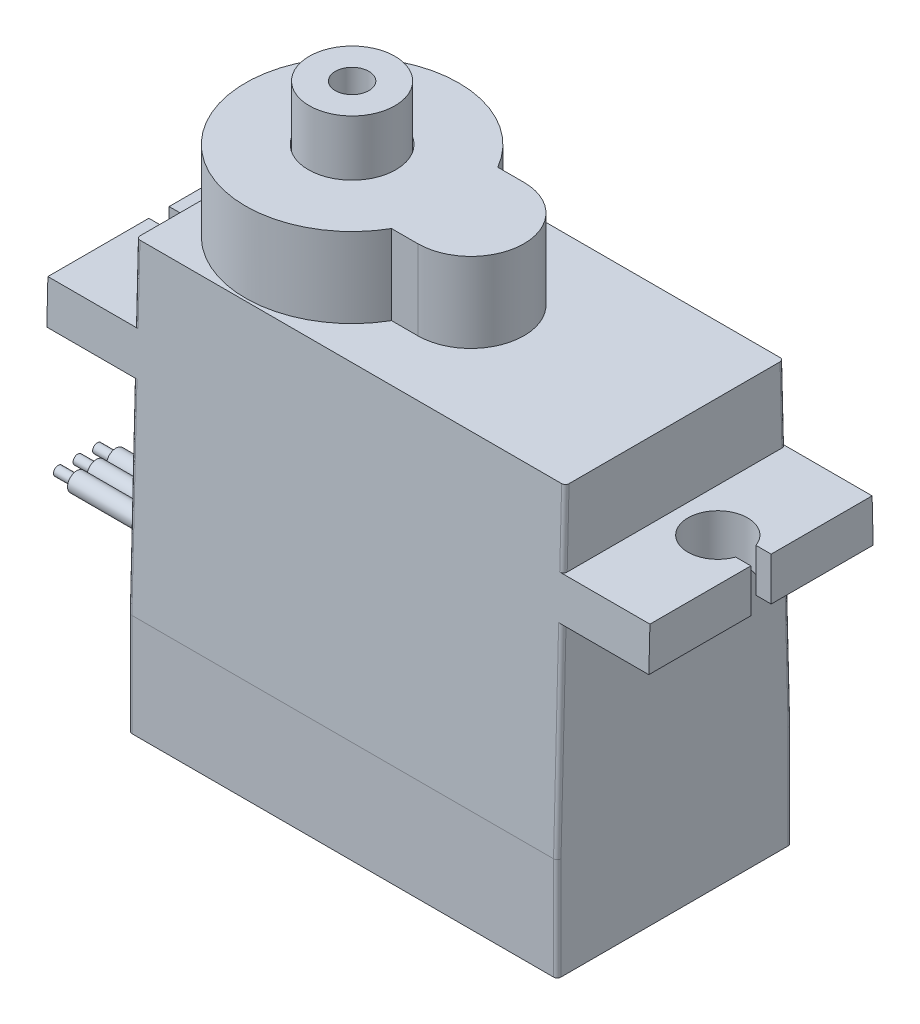
SolidWorks part; units mm, degrees
ref_plane "Front Plane" through (0, 0, 0) normal (0, 0, 1) x (1, 0, 0)
ref_plane "Top Plane" through (0, 0, 0) normal (0, 1, 0) x (1, 0, 0)
ref_plane "Right Plane" through (0, 0, 0) normal (1, 0, 0) x (0, 0, -1)
ref_axis "X-Axis" through (-88.99, 0, 0) along (1, 0, 0)
ref_axis "Y-Axis" through (0, 0, -88.99) along (0, 0, 1)
ref_axis "Z-Axis" through (0, 55, 0) along (0, -1, 0)
sketch "Sketch1" plane through (0, 0, 0) normal (0, 0, 1) x (1, 0, 0)
  line L0 (0, 0) -> (0, 12.96) construction
  line L1 (-7.13, 6.38) -> (15.9, 6.38)
  line L2 (-7.13, 6.38) -> (-7.13, 2.32)
  line L3 (-7.13, -16.34) -> (15.9, -16.34)
  line L4 (15.9, 6.38) -> (15.9, 2.32)
  line L5 (15.9, 2.32) -> (20.54, 2.32)
  line L6 (-11.77, 2.32) -> (-7.13, 2.32)
  line L7 (-11.77, 2.32) -> (-11.77, 0)
  line L8 (-11.77, 0) -> (-7.13, 0)
  line L9 (20.54, 2.32) -> (20.54, 0)
  line L10 (15.9, 0) -> (20.54, 0)
  line L11 (-7.13, 0) -> (-7.13, -16.34)
  line L12 (15.9, 0) -> (15.9, -16.34)
  line L14 (15.9, 0) -> (-7.13, 0) construction
  point P3 (4.385, 0)
  dimension "D1" = 2.32
  dimension "D2" = 32.31
  dimension "D3" = 23.03
  dimension "D4" = 16.34
  dimension "D5" = 22.72
  dimension "D6" = 7.13
  dimension "D7" = 15.9
  dimension "D10" = 29.3
  dimension "D11" = 4.385
extrude "Boss-Extrude1" add sketch "Sketch1" along normal mid plane 12.59
sketch "Sketch2" plane through (0, 6.38, 0) normal (0, 1, 0) x (1, 0, 0)
  line L0 (-1.405, 0) -> (4.97, 0) construction
  line L1 (3.5602, -2.85) -> (4.97, -2.85)
  line L2 (4.97, 2.85) -> (3.5602, 2.85)
  line L3 (-1.405, 0) -> (-7.13, 0) construction
  line L4 (4.97, 0) -> (7.82, 0) construction
  line L5 (-7.13, -6.295) -> (-7.13, 6.295) construction
  arc A0 (3.5602, 2.85) -> (3.5602, -2.85) centre (-1.405, 0) ccw
  arc A1 (4.97, -2.85) -> (4.97, 2.85) centre (4.97, 0) ccw
  dimension "D1" = 11.45
  dimension "D2" = 5.7
  dimension "D3" = 14.95
extrude "Boss-Extrude2" add sketch "Sketch2" along normal blind 4.28
sketch "Sketch11" plane through (-11.77, 0, 0) normal (-1, 0, 0) x (0, 0, 1)
  line L0 (-5.86, 6.38) -> (-6.295, -10.84)
  line L1 (0, 6.38) -> (-6.295, 6.38) construction
  line L2 (6.295, -16.34) -> (-6.295, -16.34) construction
  line L3 (-6.295, 0) -> (-6.295, -16.34) construction
  line L4 (-5.86, 6.38) -> (-6.295, 6.38)
  line L5 (-6.295, 6.38) -> (-6.295, -10.84)
  dimension "D1" = 5.86
  dimension "D2" = 5.5
extrude "Cut-Extrude4" cut sketch "Sketch11" against normal through all
mirror "Mirror1" about plane through (0, 0, 0) normal (0, 0, 1) of "Cut-Extrude4"
sketch "Sketch4" plane through (0, 0, 0) normal (0, 1, 0) x (1, 0, 0)
  line L0 (-7.13, 0) -> (-9.45, 0) construction
  line L1 (-11.77, -5.9626) -> (-11.77, 5.9626) construction
  line L2 (-10.2585, 0.545) -> (-11.77, 0.545)
  line L3 (-10.2585, 0.545) -> (-10.2585, -0.545)
  line L4 (-10.2585, -0.545) -> (-11.77, -0.545)
  line L5 (-11.77, 0.545) -> (-11.77, -0.545)
  line L8 (-9.45, 0) -> (-10.2585, 0) construction
  line L9 (-9.45, 0) -> (-11.77, 0) construction
  arc A0 (3.5602, 2.85) -> (3.5602, -2.85) centre (-1.405, 0) ccw construction
  circle A1 centre (-9.45, 0) radius 0.975
  dimension "D1" = 1.09
  dimension "D2" = 1.95
extrude "Cut-Extrude1" cut sketch "Sketch4" along normal through all contours A1 | L4 L5 L2 L3
sketch "Sketch14" plane through (0, 0.152, 6.0173) normal (0, 0.0253, 0.9997) x (1, 0, 0)
  line L0 (4.385, -10.9955) -> (-7.13, -10.9955) construction
  line L1 (15.9, -10.9955) -> (-7.13, -10.9955) construction
ref_plane "Plane1" through (4.385, -10.84, 6.295) normal (-1, 0, 0) x (0, 0, 1)
mirror "Mirror2" about plane through (4.385, -10.84, 6.295) normal (-1, 0, 0) of "Cut-Extrude1"
sketch "Sketch5" plane through (0, -16.34, 0) normal (0, -1, 0) x (1, 0, 0)
  line L0 (15.9, 6.295) -> (-7.13, -6.295) construction
  line L17 (-5.49, 4.35) -> (14.26, 4.35) construction
  line L18 (-5.49, 4.35) -> (-5.49, -4.35) construction
  line L19 (-5.49, -4.35) -> (14.26, -4.35) construction
  line L20 (14.26, 4.35) -> (14.26, -4.35) construction
  line L21 (-5.49, 4.35) -> (14.26, -4.35) construction
  circle A0 centre (-5.49, 4.35) radius 1
  circle A1 centre (-5.49, -4.35) radius 1
  circle A2 centre (14.26, -4.35) radius 1
  circle A3 centre (14.26, 4.35) radius 1
  circle A4 centre (-5.49, 4.35) radius 0.975
  circle A5 centre (-5.49, -4.35) radius 0.975
  circle A6 centre (14.26, -4.35) radius 0.975
  circle A7 centre (14.26, 4.35) radius 0.975
  point P36 (4.385, 0)
  dimension "D1" = 0.025
  dimension "D4" = 1.95
  dimension "D5" = 19.75
  dimension "D6" = 8.7
extrude "Cut-Extrude2" cut sketch "Sketch5" against normal blind 1
sketch "Sketch6" plane through (-7.13, 0, 0) normal (-1, 0, 0) x (0, 0, 1)
  line L0 (-1.05, -11.34) -> (1.05, -11.34) construction
  line L1 (0, -11.84) -> (0, -16.34) construction
  line L3 (6.295, -16.34) -> (-6.295, -16.34) construction
  circle A0 centre (0, -11.34) radius 0.5
  circle A1 centre (1.05, -11.34) radius 0.5
  circle A2 centre (-1.05, -11.34) radius 0.5
  dimension "D3" = 1
  dimension "D1" = 4.5
  dimension "D2" = 2.1
extrude "Boss-Extrude4" add sketch "Sketch6" along normal blind 8
sketch "Sketch7" plane through (-15.13, 0, 0) normal (-1, 0, 0) x (0, 0, 1)
  circle A0 centre (0, -11.34) radius 0.25
  circle A1 centre (1.05, -11.34) radius 0.25
  circle A2 centre (-1.05, -11.34) radius 0.25
  dimension "D1" = 0.5
extrude "Boss-Extrude5" add sketch "Sketch7" along normal blind 1
sketch "Sketch3" plane through (0, 10.66, 0) normal (0, 1, 0) x (1, 0, 0)
  line L0 (4.7718, -0.52) -> (4.97, -0.52)
  line L1 (4.97, 0.52) -> (4.7718, 0.52)
  line L2 (5.49, 0) -> (7.82, 0) construction
  line L3 (-4.8, 0) -> (-7.13, 0) construction
  arc A0 (4.7718, 0.52) -> (4.7718, -0.52) centre (0, 0) ccw
  arc A1 (4.97, -0.52) -> (4.97, 0.52) centre (4.97, 0) ccw
  arc A2 (4.97, -2.85) -> (4.97, 2.85) centre (4.97, 0) ccw construction
  arc A3 (3.5602, 2.85) -> (3.5602, -2.85) centre (-1.405, 0) ccw construction
  dimension "D1" = 9.6
fillet "Fillet1" radius 0.3 4 edges at (14.26, -16.34, -5.325) (14.26, -16.34, 3.375) (-5.49, -16.34, -5.325) (-5.49, -16.34, 3.375)
fillet "Fillet3" radius 0.2 12 edges at (15.9, -13.59, -6.295) (15.9, -13.59, 6.295) (-7.13, -13.59, -6.295) (-7.13, -13.59, 6.295) (-7.13, -5.42, 6.1581) (-7.13, -5.42, -6.1581) (15.9, -5.42, 6.1581) (15.9, -5.42, -6.1581) (15.9, 4.35, -5.9113) (15.9, 4.35, 5.9113) (-7.13, 4.35, -5.9113) (-7.13, 4.35, 5.9113)
sketch "Sketch12" plane through (0, 10.66, 0) normal (0, 1, 0) x (1, 0, 0)
  circle A0 centre (-1.405, 0) radius 2.3
  circle A1 centre (-1.405, 0) radius 0.9
  dimension "D1" = 4.6
  dimension "D2" = 1.8
extrude "Boss-Extrude6" add sketch "Sketch12" along normal blind 2.95 and the other way blind 1 separate body
sketch "Sketch13" plane through (0, 13.61, 0) normal (0, 1, 0) x (1, 0, 0)
  circle A0 centre (-1.405, 0) radius 2.35
  dimension "D1" = 4.7
extrude "Cut-Extrude5" cut sketch "Sketch13" against normal blind 5
sketch "Sketch15" plane through (0, 2.32, 0) normal (0, 1, 0) x (1, 0, 0)
  circle A0 centre (18.22, 0) radius 1.6
  dimension "D1" = 3.2
extrude "Cut-Extrude6" cut sketch "Sketch15" against normal blind 10
sketch "Sketch16" plane through (0, 2.32, 0) normal (0, 1, 0) x (1, 0, 0)
  circle A0 centre (-9.45, 0) radius 1.6
  dimension "D1" = 3.2
extrude "Cut-Extrude7" cut sketch "Sketch16" against normal blind 10
